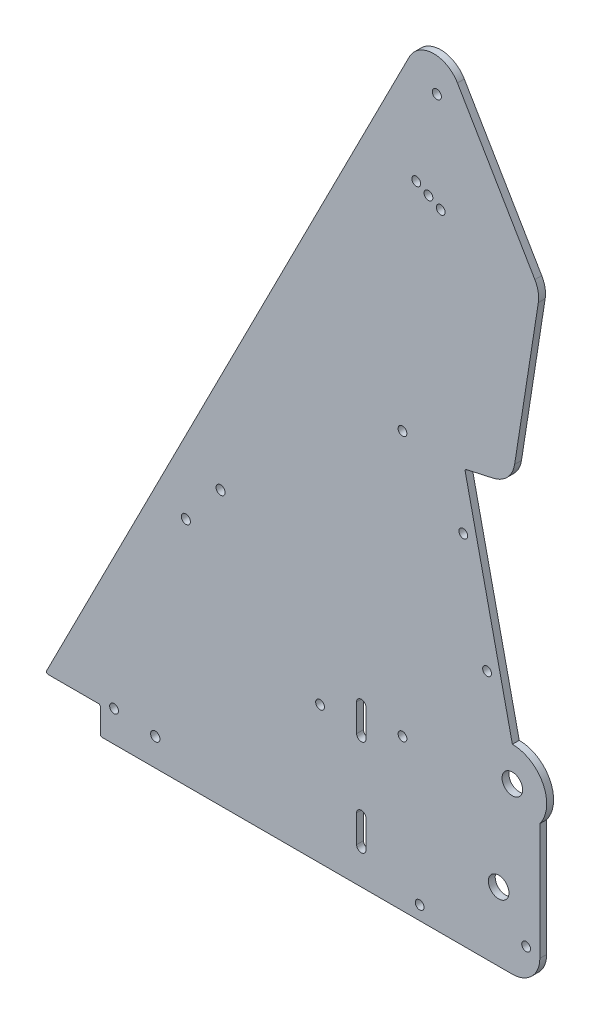
SolidWorks part; units mm, degrees
other "Markup1"
sketch "Sketch5"
ref_plane "Front Plane" through (0, 0, 0) normal (0, 0, 1) x (1, 0, 0)
ref_plane "Top Plane" through (0, 0, 0) normal (0, 1, 0) x (1, 0, 0)
ref_plane "Right Plane" through (0, 0, 0) normal (1, 0, 0) x (0, 0, -1)
sketch "Sketch1" plane through (0, 0, 0) normal (0, 0, 1) x (1, 0, 0)
  line L1 (228.6, -12.7) -> (228.6, 53.975)
  line L2 (178.7547, 351.4131) -> (0, 0)
  line L3 (228.6, 266.7) -> (178.7547, 351.4131)
  line L5 (0, 0) -> (25.4, 0)
  line L6 (25.4, 0) -> (25.4, -12.7)
  line L7 (25.4, -12.7) -> (228.6, -12.7)
  line L9 (215.9, 79.375) -> (193.9097, 178.5667)
  line L10 (193.9097, 178.5667) -> (215.6079, 183.377)
  line L11 (215.6079, 183.377) -> (228.6, 266.7)
  arc A0 (228.6, 53.975) -> (215.9, 79.375) centre (215.9, 63.5) ccw
  dimension "D7" = 12.7
  dimension "D8" = 76.2
  dimension "D10" = 31.75
  dimension "D2" = 279.4
  dimension "D3" = 25.4
  dimension "D4" = 215.9
  dimension "D5" = 394.2644
  dimension "D6" = 203.2
  dimension "D9" = 63.039
  dimension "D11" = 101.6
  dimension "D12" = 12.5
  dimension "D13" = 22.225
extrude "Boss-Extrude1" add sketch "Sketch1" along normal blind 3.175
sketch "Sketch2" plane through (0, 0, 3.175) normal (0, 0, 1) x (1, 0, 0)
  line L0 (178.7547, 351.4131) -> (0, 0) construction
  line L1 (25.4, -12.7) -> (228.6, -12.7) construction
  line L2 (215.9, 79.375) -> (193.9097, 178.5667) construction
  line L3 (193.9097, 178.5667) -> (215.6079, 183.377) construction
  line L4 (215.9, 79.375) -> (193.9097, 178.5667) construction
  line L10 (228.6, -12.7) -> (228.6, 53.975) construction
  circle A0 centre (64.9432, 94.0578) radius 2.0955
  circle A1 centre (180.975, 322.1643) radius 2.0955
  circle A2 centre (81.0071, 113.733) radius 2.0955
  circle A3 centre (193.2078, 152.3944) radius 2.032
  circle A4 centre (215.9, 63.5) radius 4.7625
  circle A7 centre (173.0375, -6.35) radius 2.032
  circle A8 centre (204.203, 102.7985) radius 2.032
  circle A26 centre (209.55, 19.05) radius 4.7625
  arc A30 (228.6, 53.975) -> (215.9, 79.375) centre (215.9, 63.5) ccw construction
  circle A31 centre (165.1, 179.3875) radius 2.032
  circle A32 centre (182.7697, 276.817) radius 2.032 construction
  circle A33 centre (177.1098, 279.696) radius 2.032 construction
  circle A34 centre (171.45, 282.575) radius 2.032 construction
  circle A35 centre (182.7697, 276.817) radius 2.032
  circle A36 centre (177.1098, 279.696) radius 2.032
  circle A37 centre (171.45, 282.575) radius 2.032
  dimension "D3" = 4.191
  dimension "D5" = 4.191
  dimension "D9" = 4.191
  dimension "D20" = 9.525
  dimension "D23" = 9.525
  dimension "D18" = 4.064
  dimension "D26" = 4.064
  dimension "D14" = 4.064
  dimension "D2" = 15.24
  dimension "D6" = 15.24
  dimension "D7" = 25.4
  dimension "D8" = 20.6375
  dimension "D21" = 44.45
  dimension "D22" = 6.35
  dimension "D19" = 160.3375
  dimension "D24" = 44.45
  dimension "D25" = 6.35
  dimension "D27" = 25.4
  dimension "D28" = 50.8
  dimension "D29" = 6.35
  dimension "D17" = 6.35
  dimension "D33" = 55.5625
  dimension "D15" = 114.3
  dimension "D4" = 180.975
extrude "Cut-Extrude1" cut sketch "Sketch2" against normal through all
sketch "Sketch7" plane through (0, 0, 3.175) normal (0, 0, 1) x (1, 0, 0)
  line L0 (146.05, 3.175) -> (146.05, 15.875) construction
  line L1 (143.891, 3.175) -> (143.891, 15.875)
  line L2 (148.209, 3.175) -> (148.209, 15.875)
  line L3 (146.05, 47.625) -> (146.05, 60.325) construction
  line L4 (143.891, 47.625) -> (143.891, 60.325)
  line L5 (148.209, 47.625) -> (148.209, 60.325)
  line L6 (25.4, -12.7) -> (228.6, -12.7) construction
  line L12 (228.6, -12.7) -> (228.6, 53.975) construction
  line L13 (25.4, -12.7) -> (228.6, -12.7) construction
  arc A0 (143.891, 3.175) -> (148.209, 3.175) centre (146.05, 3.175) ccw
  arc A1 (148.209, 15.875) -> (143.891, 15.875) centre (146.05, 15.875) ccw
  arc A2 (143.891, 47.625) -> (148.209, 47.625) centre (146.05, 47.625) ccw
  arc A3 (148.209, 60.325) -> (143.891, 60.325) centre (146.05, 60.325) ccw
  circle A8 centre (50.8, 0) radius 2.159
  point P2 (146.05, 9.525)
  point P9 (146.05, 53.975)
  dimension "D1" = 4.318
  dimension "D5" = 4.318
  dimension "D2" = 12.7
  dimension "D3" = 12.7
  dimension "D4" = 44.45
  dimension "D6" = 95.25
  dimension "D7" = 82.55
  dimension "D8" = 15.875
  dimension "D9" = 12.7
extrude "Cut-Extrude2" cut sketch "Sketch7" against normal through all
sketch "Sketch10" plane through (0, 0, 3.175) normal (0, 0, 1) x (1, 0, 0)
  circle A1 centre (165.1, 57.15) radius 2.032
  circle A2 centre (127, 50.8) radius 2.032
  dimension "D1" = 4.064
  dimension "D4" = 63.5
  dimension "D5" = 69.85
extrude "Cut-Extrude3" cut sketch "Sketch10" against normal up to next
fillet "Fillet1" radius 12.7 4 edges at (228.6, -12.7, 1.5875) (178.7547, 351.4131, 1.5875) (215.6079, 183.377, 1.5875) (228.6, 266.7, 1.5875)
fillet "Fillet2" radius 0.7937 4 edges at (25.4, -12.7, 1.5875) (25.4, 0, 1.5875) (193.9097, 178.5667, 1.5875) (0, 0, 1.5875)
sketch "Sketch12" plane through (0, 0, 3.175) normal (0, 0, 1) x (1, 0, 0)
  circle A0 centre (31.75, 1.5875) radius 2.032
  circle A1 centre (222.25, 1.5875) radius 2.032
  dimension "D1" = 4.064
extrude "Cut-Extrude5" cut sketch "Sketch12" against normal through all
equation "\"D6@Sketch2\"=\"D2@Sketch2\""
